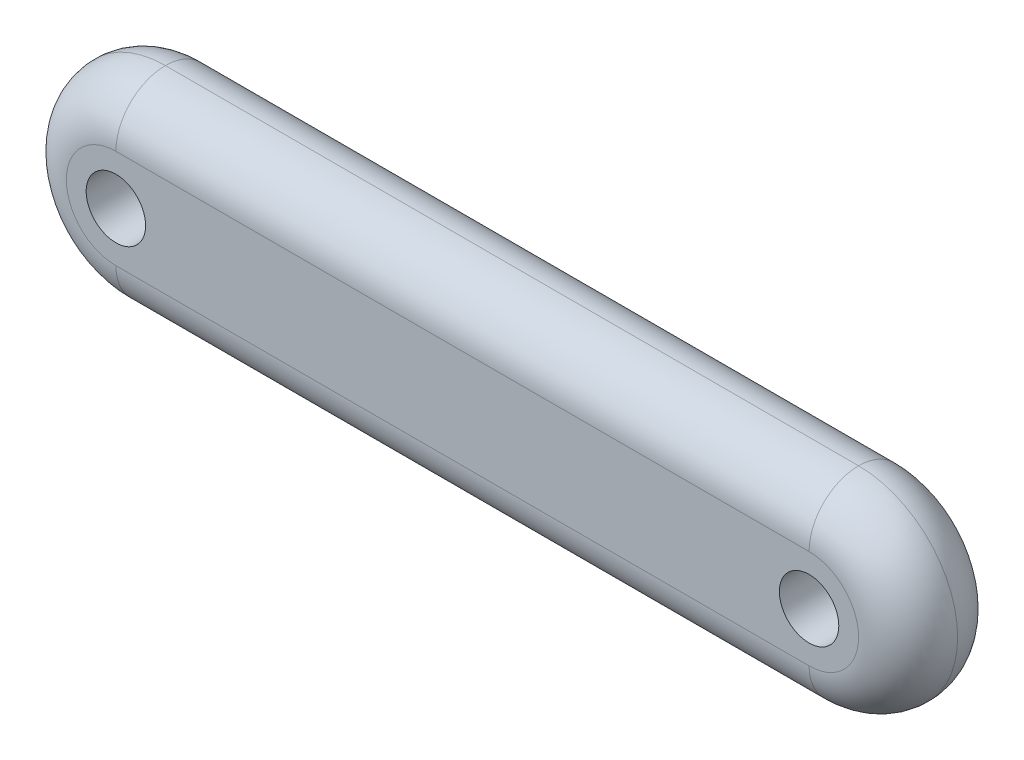
SolidWorks part; units mm, degrees
ref_plane "Front Plane" through (0, 0, 0) normal (0, 0, 1) x (1, 0, 0)
ref_plane "Top Plane" through (0, 0, 0) normal (0, 1, 0) x (1, 0, 0)
ref_plane "Right Plane" through (0, 0, 0) normal (1, 0, 0) x (0, 0, -1)
sketch "Sketch1" plane through (0, 0, 0) normal (0, 0, 1) x (1, 0, 0)
  line L0 (-70, 0) -> (70, 0) construction
  line L1 (-70, 20) -> (70, 20)
  line L2 (-70, -20) -> (70, -20)
  arc A0 (-70, 20) -> (-70, -20) centre (-70, 0) ccw
  arc A1 (70, -20) -> (70, 20) centre (70, 0) ccw
  circle A2 centre (-70, 0) radius 6
  circle A3 centre (70, 0) radius 6
  point P2 (0, 0)
  dimension "D3" = 12
  dimension "D1" = 140
  dimension "D2" = 40
extrude "Boss-Extrude2" add sketch "Sketch1" along normal blind 20
sketch "Sketch3" plane through (0, 0, 0) normal (0, 0, 1) x (1, 0, 0)
  circle A0 centre (-70, 0) radius 10
  circle A1 centre (70, 0) radius 10
extrude "Boss-Extrude3" add sketch "Sketch3" along normal blind 3
fillet "Fillet1" radius 10 4 edges at (90, 0, 20) (0, -20, 20) (-90, 0, 20) (0, 20, 20)
fillet "Fillet2" radius 10 4 edges at (90, 0, 0) (0, -20, 0) (-90, 0, 0) (0, 20, 0)
